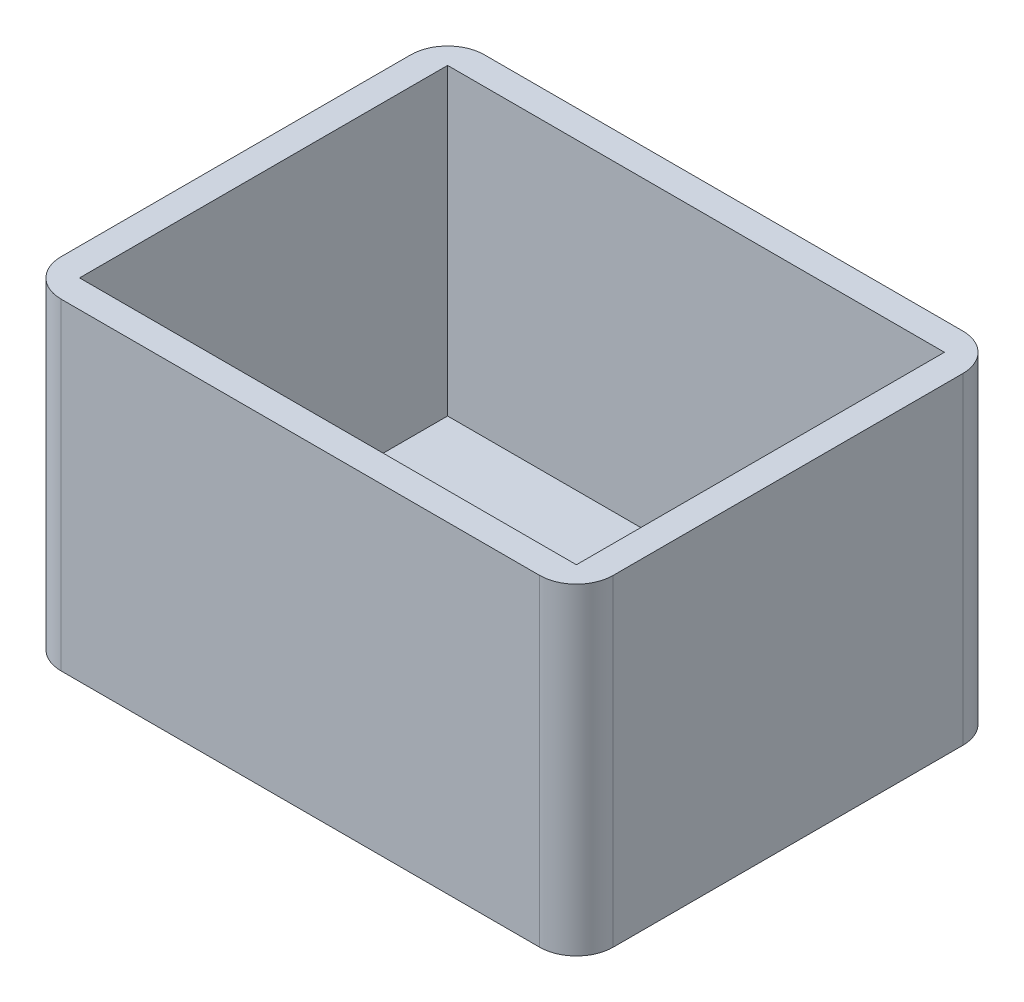
SolidWorks part; units mm, degrees
ref_plane "Plan de face" through (0, 0, 0) normal (0, 0, 1) x (1, 0, 0)
ref_plane "Plan de dessus" through (0, 0, 0) normal (0, 1, 0) x (1, 0, 0)
ref_plane "Plan de droite" through (0, 0, 0) normal (1, 0, 0) x (0, 0, -1)
sketch "Esquisse1" plane through (0, 0, 0) normal (0, 1, 0) x (1, 0, 0)
  line L0 (-117.1089, 0) -> (250, 0) construction
  line L1 (0, 46) -> (0, 0)
  line L2 (0, 0) -> (60, 0)
  line L3 (60, 0) -> (60, 46)
  line L4 (60, 46) -> (0, 46)
  line L5 (3, 46) -> (3, 0)
  line L6 (57, 46) -> (57, 0)
  line L7 (0, 43) -> (57, 43)
  line L8 (3, 3) -> (57, 3)
  line L9 (35, 13) -> (35, 11)
  line L10 (35, 13) -> (25, 13)
  line L11 (35, 13) -> (35, 33)
  line L12 (35, 33) -> (25, 33)
  line L13 (25, 13) -> (25, 33)
  line L14 (35, 11) -> (25, 11)
  line L15 (25, 11) -> (25, 13)
  line L16 (25, 33) -> (25, 35)
  line L17 (25, 35) -> (35, 35)
  line L18 (35, 35) -> (35, 33)
  point P1 (3, 3)
  point P7 (3, 46)
  point P8 (3, 0)
  point P9 (57, 46)
  point P12 (57, 0)
  point P13 (0, 43)
  point P16 (60, 43)
  point P20 (57, 3)
  dimension "D1" = 60
  dimension "D2" = 46
  dimension "D3" = 3
  dimension "D4" = 3
  dimension "D5" = 3
  dimension "D6" = 3
  dimension "D7" = 10
  dimension "D8" = 10
  dimension "D9" = 22
  dimension "D10" = 22
  dimension "D11" = 2
  dimension "D12" = 2
extrude "Boss.-Extru.9" add sketch "Esquisse1" along normal blind 2 contours L5 L8 L6 L7 region at (30, 0, -42.328)
extrude "Boss.-Extru.10" add sketch "Esquisse1<14>" along normal blind 35 contours L4 L6 L2 L3 | L5 L7 L6 L4 | L1 L7 L5 L4 | L7 L1 L2 L5 | L8 L5 L2 L6 region at (1.5, 0, -44.5) region at (1.5, 0, -21.5) region at (30, 0, -44.5) region at (58.5, 0, -23) region at (30, 0, -1.5)
sketch "Esquisse1<14>" plane through (0, 0, 0) normal (0, 1, 0) x (1, 0, 0) same geometry as "Esquisse1"
fillet "Congé14" radius 4 4 edges at (60, 17.5, 0) (60, 17.5, -46) (0, 17.5, -46) (0, 17.5, 0)
extrude "Boss.-Extru.12" add sketch "Esquisse1<18>" along normal blind 2 contours L18 L17 L16 L12 | L13 L10 L11 L12 | L15 L14 L9 L10 region at (30, 0, -12) region at (30, 0, -23) region at (30, 0, -34)
sketch "Esquisse1<18>" plane through (0, 0, 0) normal (0, 1, 0) x (1, 0, 0) same geometry as "Esquisse1"
extrude "Boss.-Extru.13" add sketch "Esquisse1<20>" against normal blind 2 contours L18 L17 L16 L12 | L15 L14 L9 L10 region at (30, 0, -12) region at (30, 0, -34)
sketch "Esquisse1<20>" plane through (0, 0, 0) normal (0, 1, 0) x (1, 0, 0) same geometry as "Esquisse1"
sketch "Esquisse8" plane through (0, 0, 0) normal (0, 1, 0) x (1, 0, 0)
sketch "Esquisse9" plane through (0, 0, 0) normal (0, 1, 0) x (1, 0, 0)
  line L0 (25, 33) -> (25, 35) construction
  line L1 (25, 35) -> (35, 35)
  line L2 (25, 35) -> (25, 11)
  line L3 (25, 11) -> (35, 11)
  line L4 (35, 35) -> (35, 11)
  point P5 (48, 29.0239)
extrude "Boss.-Extru.15" add sketch "Esquisse9" against normal blind 2 from offset 2 offset against normal yes
fillet "Congé15" radius 2 2 edges at (30, -4, -35) (30, -4, -11)
